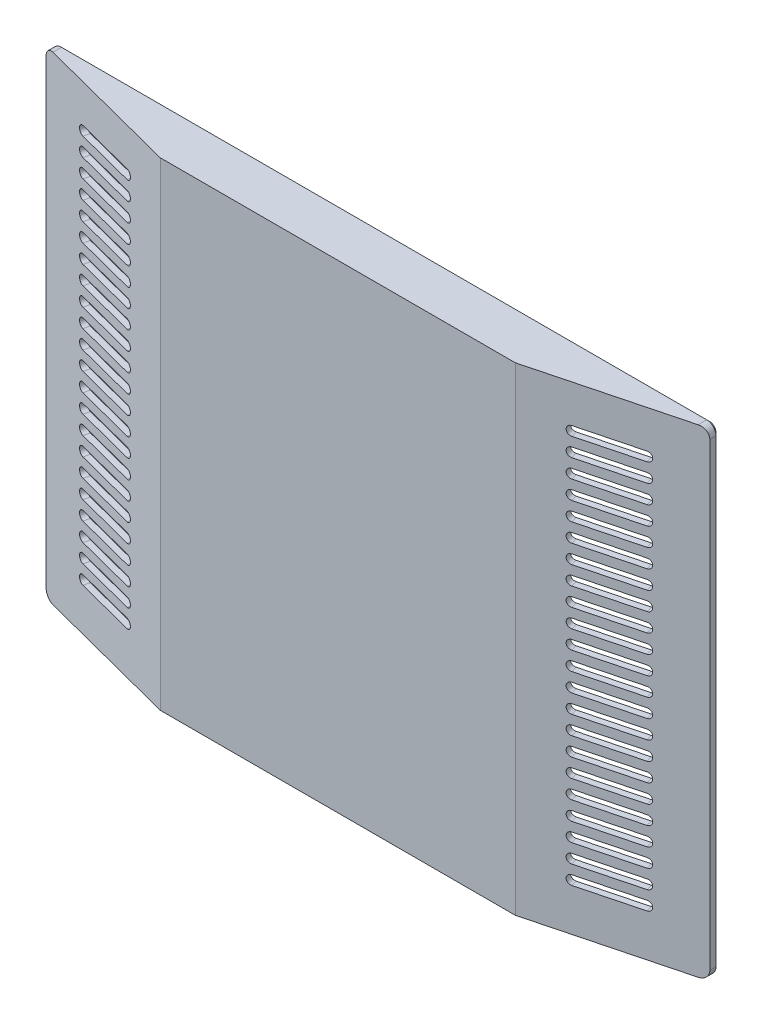
SolidWorks part; units mm, degrees
ref_plane "前视基准面" through (0, 0, 0) normal (0, 0, 1) x (1, 0, 0)
ref_plane "上视基准面" through (0, 0, 0) normal (0, 1, 0) x (1, 0, 0)
ref_plane "右视基准面" through (0, 0, 0) normal (1, 0, 0) x (0, 0, -1)
other "Configuration Table"
sketch "草图1" plane through (0, 0, 0) normal (0, 0, 1) x (1, 0, 0)
  line L1 (0, 0) -> (215, 0)
  line L2 (0, 0) -> (0, -155)
  line L3 (0, -155) -> (215, -155)
  line L4 (215, 0) -> (215, -155)
  dimension "D1" = 215
  dimension "D2" = 155
extrude "凸台-拉伸1" add sketch "草图1" along normal blind 15
sketch "草图2" plane through (0, -155, 0) normal (0, -1, 0) x (1, 0, 0)
  line L0 (0, 2) -> (50, 15)
  line L1 (0, 15) -> (0, 0) construction
  line L2 (107.5, 0) -> (107.5, 15) construction
  line L3 (0, 0) -> (215, 0) construction
  line L4 (0, 15) -> (215, 15) construction
  line L5 (50, 15) -> (0, 15)
  line L6 (0, 15) -> (0, 2)
  line L7 (165, 15) -> (215, 15)
  line L8 (215, 2) -> (165, 15)
  line L9 (215, 15) -> (215, 2)
  dimension "D1" = 2
  dimension "D2" = 50
extrude "切除-拉伸1" cut sketch "草图2" against normal blind 155
fillet "圆角1" radius 3 4 edges at (215, 0, 1) (215, -155, 1) (0, 0, 1) (0, -155, 1)
shell "抽壳1" thickness 2 removed face at (107.5, -77.5, 0)
sketch "草图3" plane through (-0.4871, 0, 1.8734) normal (-0.2516, 0, 0.9678) x (0.9678, 0, 0.2516)
  line L0 (17.1656, -13.75) -> (37.1656, -13.75) construction
  line L1 (17.1656, -12.25) -> (37.1656, -12.25)
  line L2 (17.1656, -15.25) -> (37.1656, -15.25)
  line L3 (3.603, 0) -> (52.1656, 0) construction
  line L5 (52.1656, 0) -> (52.1656, -155) construction
  line L6 (17.1656, -19.75) -> (37.1656, -19.75) construction
  line L7 (17.1656, -18.25) -> (37.1656, -18.25)
  line L8 (17.1656, -21.25) -> (37.1656, -21.25)
  line L9 (17.1656, -25.75) -> (37.1656, -25.75) construction
  line L10 (17.1656, -24.25) -> (37.1656, -24.25)
  line L11 (17.1656, -27.25) -> (37.1656, -27.25)
  line L12 (17.1656, -31.75) -> (37.1656, -31.75) construction
  line L13 (17.1656, -30.25) -> (37.1656, -30.25)
  line L14 (17.1656, -33.25) -> (37.1656, -33.25)
  line L15 (17.1656, -37.75) -> (37.1656, -37.75) construction
  line L16 (17.1656, -36.25) -> (37.1656, -36.25)
  line L17 (17.1656, -39.25) -> (37.1656, -39.25)
  line L18 (17.1656, -43.75) -> (37.1656, -43.75) construction
  line L19 (17.1656, -42.25) -> (37.1656, -42.25)
  line L20 (17.1656, -45.25) -> (37.1656, -45.25)
  line L21 (17.1656, -49.75) -> (37.1656, -49.75) construction
  line L22 (17.1656, -48.25) -> (37.1656, -48.25)
  line L23 (17.1656, -51.25) -> (37.1656, -51.25)
  line L24 (17.1656, -55.75) -> (37.1656, -55.75) construction
  line L25 (17.1656, -54.25) -> (37.1656, -54.25)
  line L26 (17.1656, -57.25) -> (37.1656, -57.25)
  line L27 (17.1656, -61.75) -> (37.1656, -61.75) construction
  line L28 (17.1656, -60.25) -> (37.1656, -60.25)
  line L29 (17.1656, -63.25) -> (37.1656, -63.25)
  line L30 (17.1656, -67.75) -> (37.1656, -67.75) construction
  line L31 (17.1656, -66.25) -> (37.1656, -66.25)
  line L32 (17.1656, -69.25) -> (37.1656, -69.25)
  line L33 (17.1656, -73.75) -> (37.1656, -73.75) construction
  line L34 (17.1656, -72.25) -> (37.1656, -72.25)
  line L35 (17.1656, -75.25) -> (37.1656, -75.25)
  line L36 (17.1656, -79.75) -> (37.1656, -79.75) construction
  line L37 (17.1656, -78.25) -> (37.1656, -78.25)
  line L38 (17.1656, -81.25) -> (37.1656, -81.25)
  line L39 (17.1656, -85.75) -> (37.1656, -85.75) construction
  line L40 (17.1656, -84.25) -> (37.1656, -84.25)
  line L41 (17.1656, -87.25) -> (37.1656, -87.25)
  line L42 (17.1656, -91.75) -> (37.1656, -91.75) construction
  line L43 (17.1656, -90.25) -> (37.1656, -90.25)
  line L44 (17.1656, -93.25) -> (37.1656, -93.25)
  line L45 (17.1656, -97.75) -> (37.1656, -97.75) construction
  line L46 (17.1656, -96.25) -> (37.1656, -96.25)
  line L47 (17.1656, -99.25) -> (37.1656, -99.25)
  line L48 (17.1656, -103.75) -> (37.1656, -103.75) construction
  line L49 (17.1656, -102.25) -> (37.1656, -102.25)
  line L50 (17.1656, -105.25) -> (37.1656, -105.25)
  line L51 (17.1656, -109.75) -> (37.1656, -109.75) construction
  line L52 (17.1656, -108.25) -> (37.1656, -108.25)
  line L53 (17.1656, -111.25) -> (37.1656, -111.25)
  line L54 (17.1656, -115.75) -> (37.1656, -115.75) construction
  line L55 (17.1656, -114.25) -> (37.1656, -114.25)
  line L56 (17.1656, -117.25) -> (37.1656, -117.25)
  line L57 (17.1656, -121.75) -> (37.1656, -121.75) construction
  line L58 (17.1656, -120.25) -> (37.1656, -120.25)
  line L59 (17.1656, -123.25) -> (37.1656, -123.25)
  line L60 (17.1656, -127.75) -> (37.1656, -127.75) construction
  line L61 (17.1656, -126.25) -> (37.1656, -126.25)
  line L62 (17.1656, -129.25) -> (37.1656, -129.25)
  line L63 (17.1656, -133.75) -> (37.1656, -133.75) construction
  line L64 (17.1656, -132.25) -> (37.1656, -132.25)
  line L65 (17.1656, -135.25) -> (37.1656, -135.25)
  line L66 (17.1656, -139.75) -> (37.1656, -139.75) construction
  line L67 (17.1656, -138.25) -> (37.1656, -138.25)
  line L68 (17.1656, -141.25) -> (37.1656, -141.25)
  arc A0 (17.1656, -12.25) -> (17.1656, -15.25) centre (17.1656, -13.75) ccw
  arc A1 (37.1656, -15.25) -> (37.1656, -12.25) centre (37.1656, -13.75) ccw
  arc A2 (17.1656, -18.25) -> (17.1656, -21.25) centre (17.1656, -19.75) ccw
  arc A3 (37.1656, -21.25) -> (37.1656, -18.25) centre (37.1656, -19.75) ccw
  arc A4 (17.1656, -24.25) -> (17.1656, -27.25) centre (17.1656, -25.75) ccw
  arc A5 (37.1656, -27.25) -> (37.1656, -24.25) centre (37.1656, -25.75) ccw
  arc A6 (17.1656, -30.25) -> (17.1656, -33.25) centre (17.1656, -31.75) ccw
  arc A7 (37.1656, -33.25) -> (37.1656, -30.25) centre (37.1656, -31.75) ccw
  arc A8 (17.1656, -36.25) -> (17.1656, -39.25) centre (17.1656, -37.75) ccw
  arc A9 (37.1656, -39.25) -> (37.1656, -36.25) centre (37.1656, -37.75) ccw
  arc A10 (17.1656, -42.25) -> (17.1656, -45.25) centre (17.1656, -43.75) ccw
  arc A11 (37.1656, -45.25) -> (37.1656, -42.25) centre (37.1656, -43.75) ccw
  arc A12 (17.1656, -48.25) -> (17.1656, -51.25) centre (17.1656, -49.75) ccw
  arc A13 (37.1656, -51.25) -> (37.1656, -48.25) centre (37.1656, -49.75) ccw
  arc A14 (17.1656, -54.25) -> (17.1656, -57.25) centre (17.1656, -55.75) ccw
  arc A15 (37.1656, -57.25) -> (37.1656, -54.25) centre (37.1656, -55.75) ccw
  arc A16 (17.1656, -60.25) -> (17.1656, -63.25) centre (17.1656, -61.75) ccw
  arc A17 (37.1656, -63.25) -> (37.1656, -60.25) centre (37.1656, -61.75) ccw
  arc A18 (17.1656, -66.25) -> (17.1656, -69.25) centre (17.1656, -67.75) ccw
  arc A19 (37.1656, -69.25) -> (37.1656, -66.25) centre (37.1656, -67.75) ccw
  arc A20 (17.1656, -72.25) -> (17.1656, -75.25) centre (17.1656, -73.75) ccw
  arc A21 (37.1656, -75.25) -> (37.1656, -72.25) centre (37.1656, -73.75) ccw
  arc A22 (17.1656, -78.25) -> (17.1656, -81.25) centre (17.1656, -79.75) ccw
  arc A23 (37.1656, -81.25) -> (37.1656, -78.25) centre (37.1656, -79.75) ccw
  arc A24 (17.1656, -84.25) -> (17.1656, -87.25) centre (17.1656, -85.75) ccw
  arc A25 (37.1656, -87.25) -> (37.1656, -84.25) centre (37.1656, -85.75) ccw
  arc A26 (17.1656, -90.25) -> (17.1656, -93.25) centre (17.1656, -91.75) ccw
  arc A27 (37.1656, -93.25) -> (37.1656, -90.25) centre (37.1656, -91.75) ccw
  arc A28 (17.1656, -96.25) -> (17.1656, -99.25) centre (17.1656, -97.75) ccw
  arc A29 (37.1656, -99.25) -> (37.1656, -96.25) centre (37.1656, -97.75) ccw
  arc A30 (17.1656, -102.25) -> (17.1656, -105.25) centre (17.1656, -103.75) ccw
  arc A31 (37.1656, -105.25) -> (37.1656, -102.25) centre (37.1656, -103.75) ccw
  arc A32 (17.1656, -108.25) -> (17.1656, -111.25) centre (17.1656, -109.75) ccw
  arc A33 (37.1656, -111.25) -> (37.1656, -108.25) centre (37.1656, -109.75) ccw
  arc A34 (17.1656, -114.25) -> (17.1656, -117.25) centre (17.1656, -115.75) ccw
  arc A35 (37.1656, -117.25) -> (37.1656, -114.25) centre (37.1656, -115.75) ccw
  arc A36 (17.1656, -120.25) -> (17.1656, -123.25) centre (17.1656, -121.75) ccw
  arc A37 (37.1656, -123.25) -> (37.1656, -120.25) centre (37.1656, -121.75) ccw
  arc A38 (17.1656, -126.25) -> (17.1656, -129.25) centre (17.1656, -127.75) ccw
  arc A39 (37.1656, -129.25) -> (37.1656, -126.25) centre (37.1656, -127.75) ccw
  arc A40 (17.1656, -132.25) -> (17.1656, -135.25) centre (17.1656, -133.75) ccw
  arc A41 (37.1656, -135.25) -> (37.1656, -132.25) centre (37.1656, -133.75) ccw
  arc A42 (17.1656, -138.25) -> (17.1656, -141.25) centre (17.1656, -139.75) ccw
  arc A43 (37.1656, -141.25) -> (37.1656, -138.25) centre (37.1656, -139.75) ccw
  point P2 (27.1656, -13.75)
  point P14 (27.1656, -19.75)
  point P21 (27.1656, -25.75)
  point P28 (27.1656, -31.75)
  point P35 (27.1656, -37.75)
  point P42 (27.1656, -43.75)
  point P49 (27.1656, -49.75)
  point P56 (27.1656, -55.75)
  point P63 (27.1656, -61.75)
  point P70 (27.1656, -67.75)
  point P77 (27.1656, -73.75)
  point P84 (27.1656, -79.75)
  point P91 (27.1656, -85.75)
  point P98 (27.1656, -91.75)
  point P105 (27.1656, -97.75)
  point P112 (27.1656, -103.75)
  point P119 (27.1656, -109.75)
  point P126 (27.1656, -115.75)
  point P133 (27.1656, -121.75)
  point P140 (27.1656, -127.75)
  point P147 (27.1656, -133.75)
  point P154 (27.1656, -139.75)
  dimension "D2" = 1.5
  dimension "D1" = 13.75
  dimension "D3" = 20
  dimension "D4" = 15
  dimension "D5" = 22
extrude "切除-拉伸2" cut sketch "草图3" against normal blind 3
ref_plane "基准面1" through (107.5, 0, 0) normal (1, 0, 0) x (0, 0, -1)
mirror "镜向1" about plane through (107.5, 0, 0) normal (1, 0, 0) of "切除-拉伸2"
sketch "草图4" plane through (0, 0, 0) normal (0, 0, -1) x (-1, 0, 0)
  line L0 (-3, -2) -> (-212, -2)
  line L1 (-213, -3) -> (-213, -152)
  line L2 (-212, -153) -> (-3, -153)
  line L3 (-2, -152) -> (-2, -3)
  line L12 (-3, -1) -> (-212, -1)
  line L13 (-214, -3) -> (-214, -152)
  line L14 (-212, -154) -> (-3, -154)
  line L15 (-1, -152) -> (-1, -3)
  arc A0 (-212, -2) -> (-213, -3) centre (-212, -3) ccw
  arc A1 (-213, -152) -> (-212, -153) centre (-212, -152) ccw
  arc A2 (-3, -153) -> (-2, -152) centre (-3, -152) ccw
  arc A3 (-2, -3) -> (-3, -2) centre (-3, -3) ccw
  arc A12 (-212, -1) -> (-214, -3) centre (-212, -3) ccw
  arc A13 (-214, -152) -> (-212, -154) centre (-212, -152) ccw
  arc A14 (-3, -154) -> (-1, -152) centre (-3, -152) ccw
  arc A15 (-1, -3) -> (-3, -1) centre (-3, -3) ccw
  dimension "D3" = 1
extrude "凸台-拉伸2" add sketch "草图4" along normal blind 1
